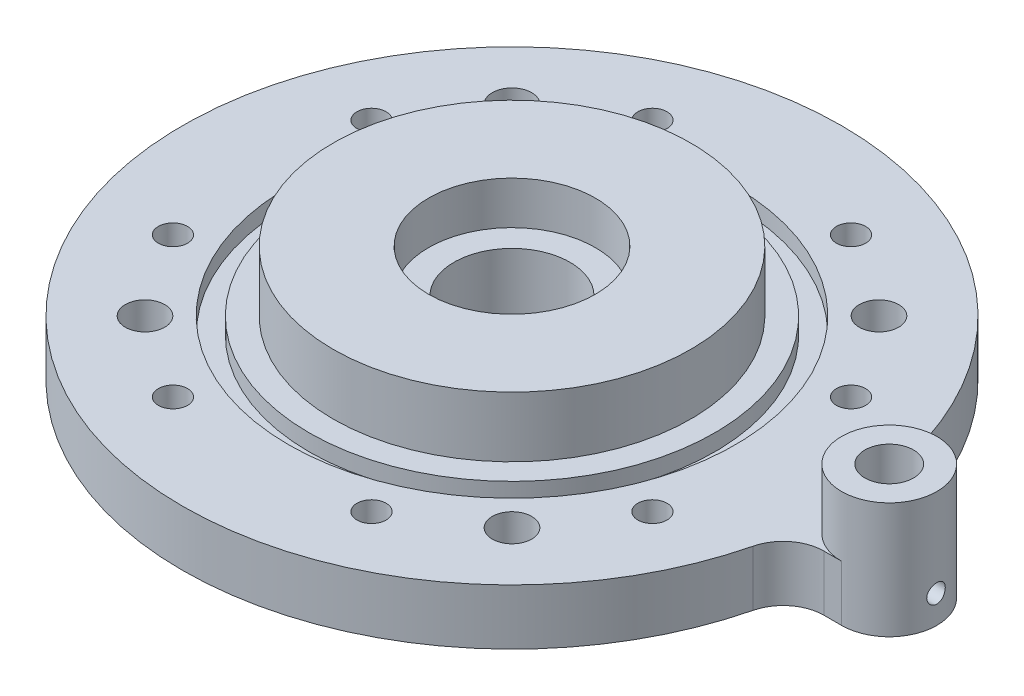
SolidWorks part; units mm, degrees
material "1060 Alloy"
ref_plane "Front" through (0, 0, 0) normal (0, 0, 1) x (1, 0, 0)
ref_plane "Top" through (0, 0, 0) normal (0, 1, 0) x (1, 0, 0)
ref_plane "Right" through (0, 0, 0) normal (1, 0, 0) x (0, 0, -1)
sketch "Sketch1" plane through (0, 0, 0) normal (0, 1, 0) x (1, 0, 0)
  line L0 (56.45, 0) -> (64.6172, 0) construction
  line L1 (61.6105, 8.1672) -> (64.6172, 8.1672)
  line L2 (61.6105, -8.1672) -> (64.6172, -8.1672)
  line L3 (56.45, 0) -> (72.7844, 0) construction
  arc A0 (54.8135, 13.4939) -> (54.8135, -13.4939) centre (0, 0) ccw
  circle A1 centre (0, 0) radius 56.45 construction
  arc A2 (64.6172, -8.1672) -> (64.6172, 8.1672) centre (64.6172, 0) ccw
  arc A3 (54.8135, 13.4939) -> (61.6105, 8.1672) centre (61.6105, 15.1672) ccw
  arc A4 (61.6105, -8.1672) -> (54.8135, -13.4939) centre (61.6105, -15.1672) ccw
  point P5 (34.5422, 0)
  point P10 (55.8561, 8.1672)
  dimension "D1" = 112.9
  dimension "D4" = 7
  dimension "D2" = 16.3344
  dimension "D3" = 16.3344
extrude "base" add sketch "Sketch1" along normal blind 9.525
sketch "Sketch2" plane through (0, 9.525, 0) normal (0, 1, 0) x (1, 0, 0)
  line L0 (64.6172, 8.1672) -> (64.6172, -8.1672) construction
  circle A0 centre (0, 0) radius 30.6267
  arc A1 (64.6172, -8.1672) -> (64.6172, 8.1672) centre (64.6172, 0) ccw construction
  circle A2 centre (64.6172, 0) radius 8.1672
  circle A3 centre (64.6172, 0) radius 4.1672
  dimension "D1" = 61.2534
  dimension "D2" = 8.3344
sketch "Sketch3" plane through (0, 0, 0) normal (0, -1, 0) x (1, 0, 0)
  line L0 (0, 0) -> (72.7844, 0) construction
  line L1 (0, 0) -> (39.9162, -39.9162) construction
  circle A0 centre (0, 0) radius 44.45 construction
  circle A1 centre (-31.4309, -31.4309) radius 3.3734
  circle A2 centre (-31.4309, 31.4309) radius 3.3734
  circle A3 centre (31.4309, 31.4309) radius 3.3734
  circle A4 centre (31.4309, -31.4309) radius 3.3734
  arc A5 (64.6172, -8.1672) -> (64.6172, 8.1672) centre (64.6172, 0) ccw construction
  arc A6 (54.8135, 13.4939) -> (54.8135, -13.4939) centre (0, 0) ccw construction
  point P14 (0, 0)
  dimension "D1" = 88.9
  dimension "D2" = 6.7469
  dimension "D4" = 45
  dimension "D3" = 4
extrude "square bolt holes" cut sketch "Sketch3" against normal through all
sketch "Sketch4" plane through (0, 9.525, 0) normal (0, 1, 0) x (1, 0, 0)
  line L0 (0, 0) -> (0, 44.45) construction
  line L1 (0, 44.45) -> (0, 0) construction
  line L2 (0, 0) -> (17.0103, 41.0664) construction
  circle A0 centre (0, 0) radius 44.45 construction
  circle A1 centre (17.0103, 41.0664) radius 2.5
  dimension "D1" = 88.9
  dimension "D3" = 5
  dimension "D2" = 22.5
extrude "housing bolts" cut sketch "Sketch4" against normal blind 44.33
pattern_circular "CirPattern1" count 8 over 360 about axis through (0, 9.525, 0) along (0, 1, 0) of "housing bolts"
extrude "impeller cavity riser" add sketch "Sketch2" along normal blind 10.3422
sketch "Sketch5" plane through (0, 19.8672, 0) normal (0, 1, 0) x (1, 0, 0)
  circle A0 centre (0, 0) radius 14.2875
  dimension "D1" = 28.575
extrude "seal bore" cut sketch "Sketch5" against normal blind 7.35
sketch "Sketch6" plane through (0, 12.5172, 0) normal (0, 1, 0) x (1, 0, 0)
  circle A0 centre (0, 0) radius 9.9375
  dimension "D1" = 19.875
extrude "bore" cut sketch "Sketch6" against normal blind 39.3
sketch "pressure tap plane alignment" plane through (0, 0, 0) normal (0, -1, 0) x (1, 0, 0)
  line L1 (0, 0) -> (56.45, 0) construction
  line L2 (56.45, 0) -> (56.45, 56.45) construction
  line L3 (56.45, 56.45) -> (0, 56.45) construction
  circle A0 centre (0, 0) radius 56.45 construction
  circle A1 centre (0, 0) radius 56.45 construction
ref_plane "pressure tap plane" through (56.45, 0, 0) normal (1, 0, 0) x (0, 0, -1)
sketch "Sketch9" plane through (56.45, 0, 0) normal (1, 0, 0) x (0, 0, -1)
  line L0 (0, 0) -> (0, 9.525) construction
  line L1 (56.45, 9.525) -> (-56.45, 9.525) construction
  circle A0 centre (0, 4.7625) radius 1.5875
  dimension "D1" = 3.175
extrude "pressure tap" cut sketch "Sketch9" against normal blind 56.45 and the other way through all
sketch "Sketch10" plane through (0, 9.525, 0) normal (0, 1, 0) x (1, 0, 0)
  circle A0 centre (64.6172, 0) radius 1.5875
  dimension "D1" = 3.175
extrude "pressure tap vertical hole" cut sketch "Sketch10" against normal blind 6.35
sketch "Sketch12" plane through (0, 9.525, 0) normal (0, 1, 0) x (1, 0, 0)
  circle A0 centre (0, 0) radius 34.7218
  circle A1 centre (0, 0) radius 38.2524
  dimension "D1" = 76.5048
  dimension "D2" = 69.4436
extrude "Cut-Extrude1" cut sketch "Sketch12" against normal blind 2.8245
equation "\"de\" = 0.426in\t\t\t'entrance eye diameter"
equation "\"d2\" = 2.097in \t\t\t'outer diameter of the impeller"
equation "\"d_exit\" = 0.18in \t\t'volute throat aka D4"
equation "\"theta\" = 25\t\t\t'angle of blades from inner to outer "
equation "\"impeller upper clearance\"= .5mm"
equation "\"impeller horizontal clearance\"= (\"d2\"*1.15 - \"d2\")/2 \t\t'clearance based on D2-D3 ratio for circular volute, ranges 1.15 to 1.2"
equation "\"impeller bottom clearance\"= .5mm"
equation "\"impeller base thickness\"= 2mm"
equation "\"impeller dowel diameter\" = 2mm"
equation "\"impeller bolt head diameter\" = \"m4 head bore diameter\""
equation "\"impeller bolt head depth\" = 4mm"
equation "\"impeller bolt stop depth\" = 3mm"
equation "\"impeller bolt bore\" = \"m4 clearance\""
equation "\"impeller shaft bore depth\" = 12mm"
equation "\"impeller shaft bore\" = 8mm"
equation "\"impeller boss depth\" = \"impeller shaft bore depth\"+\"impeller bolt stop depth\"+\"impeller bolt head depth\"-\"impeller base thickness\""
equation "\"impeller boss diameter\" = \"upper seal ID\""
equation "\"impeller dowel length\" = 2mm*2 + \"impeller shaft bore\""
equation "\"coupler motor shaft hole ID\"= 8mm"
equation "\"coupler OD\"= 17mm"
equation "\"coupler length\"= 25mm"
equation "\"motor OD\" = 64mm"
equation "\"motor shaft diameter\"= 8mm"
equation "\"motor shaft pride\"= 32mm"
equation "\"motor to bearing plate distance\" = \"motor shaft pride\" + 2mm +\"coupler length\"/2"
equation "\"square plate bolt bore\" = 8mm"
equation "\"square plate bolt head diameter\" = 13.5mm"
equation "\"square plate bolt pattern diameter\"= 3.5in"
equation "\"motor mount center bore\"= \"coupler OD\"+ 4mm"
equation "\"motor mount post radius\"= ( 3 * \"square plate bolt bore\" ) / 2"
equation "\"motor mount m4 screw hole diameter\"= 4mm"
equation "\"motor mount m4 head diameter\"= 7.25mm"
equation "\"motor mount m4 head depth\"= 4mm"
equation "\"motor mount m4 pattern diamater\" = 30mm"
equation "\"motor mount plate thickness\"= 8mm + \"motor mount m4 head depth\""
equation "\"shaft coupler section diameter\" = 8mm"
equation "\"shaft coupler section length\" = \"motor to bearing plate distance\" - \"motor shaft pride\" - 2mm"
equation "\"shaft bearing section diameter\" = \"bearing ID\""
equation "\"shaft bearing section length\" = \"bearing plate stop depth\" + \"bearing depth\""
equation "\"shaft bearing stop diameter\" = \"bearing ID\" + 4mm"
equation "\"shaft bearing stop length\" = 3mm"
equation "\"impeller cavity center height\"= \"impeller bottom clearance\" + \"impeller upper clearance\" + \"impeller center height\""
equation "\"impeller cavity diameter\"= 2 * \"impeller horizontal clearance\" + \"d2\" \t\t\t\t\t\t\t\t\t'called D3 analytically"
equation "\"impeller cavity outer height\"= \"impeller bottom clearance\" + \"impeller upper clearance\" + \"impeller base thickness\" + \"b2\" \t\t'this is height at impeller diameter d2, not at d3"
equation "\"impeller housing thickness\"= \"impeller housing exit threaded diameter\" + 2*\"impeller housing outlet grip\""
equation "\"impeller housing diameter\" = \"square plate bolt pattern diameter\" + 2*\"motor mount post radius\""
equation "\"impeller housing bolt count\" = 8"
equation "\"impeller housing bolt diameter\" = \"m6 clearance\""
equation "\"impeller housing bolt pattern diameter\" = 3.5in"
equation "\"impeller housing threaded inlet diameter\" = 0.6875in \t\t'this is the 11/16 drill size for 1/2 npt fitting"
equation "\"impeller housing threaded inlet depth\"= 15mm"
equation "\"impeller housing exit threaded diameter\"= 0.6875in \t\t'this is the 11/16 drill size for 1/2 npt fitting"
equation "\"impeller housing exit threaded depth\"= 18mm"
equation "\"impeller housing diffuser conical angle\"=10"
equation "\"impeller housing diffuser tangent angle\"=5"
equation "\"impeller housing outlet grip\" = 5mm"
equation "\"D1@Sketch1\"=\"impeller housing diameter\""
equation "\"D1@base\" = \"upper seal plate thickness\""
equation "\"D1@Sketch2\"=\"impeller cavity diameter\""
equation "\"D1@Sketch3\"=\"square plate bolt pattern diameter\""
equation "\"D2@Sketch3\"=\"m8 tap\""
equation "\"D1@square bolt holes\" = \"upper seal plate thickness\" - 2mm"
equation "\"D1@Sketch4\"=\"impeller housing bolt pattern diameter\""
equation "\"D2@Sketch4\"=360/\"impeller housing bolt count\"/2"
equation "\"D3@Sketch4\"=\"m6 tap\""
equation "\"D1@CirPattern1\"=\"impeller housing bolt count\""
equation "\"D1@impeller cavity riser\" = \"upper seal plate riser\""
equation "\"D1@Sketch5\" = \"upper seal OD\""
equation "\"D1@seal bore\" = \"upper seal bore\""
equation "\"D1@Sketch6\" = \"upper seal ID\" + 4mm"
equation "\"D1@Sketch9\" = \"upper seal plate pressure hole diameter\""
equation "\"D1@pressure tap\"=\"impeller housing diameter\"/2"
equation "\"de_length\" = 10mm\t\t'entrance eye consistent length"
equation "\"square plate bolt head depth\" = 8mm"
equation "\"shaft impeller section diameter\" = \"impeller shaft bore\""
equation "\"shaft impeller section length\" = \"upper seal plate thickness\" + \"upper seal plate riser\" + \"impeller bottom clearance\" + \"impeller base thickness\" - \"impeller bolt head depth\" - \"impeller bolt stop depth\""
equation "\"impeller housing diffuser final diameter\" = .5in"
equation "\"D2@Sketch1\" = \"upper seal plate pressure tap diameter\" + \"upper seal plate pressure tap grip\" * 2"
equation "\"D3@Sketch1\" = \"upper seal plate pressure tap diameter\" + \"upper seal plate pressure tap grip\" * 2"
equation "\"D2@pressure tap\"=\"big seal plate pressure tap diameter\"/2+\"big seal plate pressure tap grip\""
equation "\"D2@Sketch2\" = \"upper seal plate pressure tap diameter\""
equation "\"D1@Sketch10\" = \"upper seal plate pressure hole diameter\""
equation "\"D1@pressure tap vertical hole\"= \"upper seal plate thickness\" / 2 + \"upper seal plate pressure hole diameter\" / 2"
equation "\"end mill size\" = 0.375in\t'for 3/8 endmill"
equation "\"m6 clearance\" = 0.234375in\t'this is 15/64 bit = 5.95mm, could use 6mm bit, B bit for 6.04mm or 1/4 bit for 6.35mm"
equation "\"m6 tap\" = 5mm\t\t\t'5mm is appropriate, could use 13/64 or #5,6,7"
equation "\"m6 head bore diameter\" = 11mm\t\t"
equation "\"m6 head bore depth\" = 7mm\t'actual is 6mm"
equation "\"m8 clearance\" = 0.3125in\t'this is 5/16in for 7.93mm, could use 8mm, O,P, or 21/64"
equation "\"m8 tap\" = 0.265625in\t\t'this is 17/64 for 6.746875mm"
equation "\"m8 head bore diameter\" = 14mm"
equation "\"m8 head bore depth\" = 9mm\t'actual is 8mm"
equation "\"ce\" = 3.14*\"de\"\t\t'entrance eye circumference"
equation "\"s_open\" = \"av\"/\"b1\"\t\t'width of open area"
equation "\"impeller center height\" = \"impeller base thickness\" + \"b1\"\t'impeller height at de"
equation "\"impeller outer height\" = \"impeller base thickness\" + \"b2\"\t'impeller height at de"
equation "\"lower seal OD\" = .917in\t\t'this is https://www.mcmaster.com/#9281k121/=174001b"
equation "\"lower seal ID\"= .375in"
equation "\"lower seal depth\" = .625in + .218in"
equation "\"lower seal bore\" = \"lower seal depth\" + 1mm"
equation "\"upper seal OD\" = 1.125in\t'this is https://www.mcmaster.com/#5154t33/=173zuau, needs to be visually inspected before machining!"
equation "\"upper seal ID\"= 0.625in"
equation "\"upper seal depth\"= .25in\t'aka height; these values need to be confirmed by inspection!! We may want to compress the height."
equation "\"upper seal bore\" = \"upper seal depth\" + 1mm"
equation "\"lower seal plate lip depth\" = 2mm"
equation "\"lower seal plate lip ID\" = \"lower seal OD\" - 3mm"
equation "\"lower seal plate thickness\" = \"lower seal plate lip depth\" + \"lower seal bore\""
equation "\"shaft lower seal section diameter\" = \"lower seal ID\""
equation "\"shaft lower seal section length\" = \"lower seal plate thickness\" + 1mm"
equation "\"upper seal plate thickness\" = \"upper seal plate pressure hole diameter\"*3"
equation "\"upper seal plate lip ID\" = \"upper seal OD\" - 3mm"
equation "\"upper seal plate riser\" = \"impeller housing thickness\"/2 - \"b2\"/2 - \"impeller base thickness\" - \t\"impeller bottom clearance\"\t\t\t'this offsets the gap under the housing"
equation "\"upper seal plate pressure hole diameter\" = .125in\t'this is 1/8 drill "
equation "\"upper seal plate pressure tap diameter\" = .328125in \t'this is 21/64 drill for a 1/8 ANPT tap"
equation "\"upper seal plate pressure tap grip\" = 4mm\t\t'this is the area around the tap so it doesn't crack"
equation "\"upper seal plate pressure tap depth\" = 12"
equation "\"bearing OD\" = 30mm"
equation "\"bearing ID\"= 10mm"
equation "\"bearing depth\"= 9mm"
equation "\"bearing outer race thickness\"= 1mm"
equation "\"bearing inner race thickness\"= 1mm"
equation "\"bearing bore\" = \"bearing depth\" + 1mm"
equation "\"z\" = 8 \t\t\t'number of blades"
equation "\"b2\" = .07in\t\t\t\t\t\t\t'tip height from disc surface at d2"
equation "\"b1\" = \"b2\" + (\"d2\"/2 - \"de\"/2)*tan(\"theta\") \t\t\t'tip height from disc surface at inlet eye"
equation "\"ae\" = 3.14*(\"de\"^2)/4\t\t'entrance eye area'"
equation "\"av_ratio\" = .325\t\t'ratio of av/ae at N_s of 470, range is .275 to .375, .325 ideal. High ratio means bigger area means smaller blades"
equation "\"av\" = \"ae\"*\"av_ratio\"\t\t'area between just two blades"
equation "\"s\"=\"ce\" - \"z\"*\"s_open\""
equation "\"bearing plate stop ID\" = \"bearing OD\" - 4mm"
equation "\"bearing plate stop depth\" = 3mm"
equation "\"bearing plate thickness\" = \"bearing bore\" + \"bearing plate stop depth\" + \"shaft bearing stop length\""
equation "\"m4 clearance\" = 0.171875in \t'this is 11/64 bit for 4.36mm"
equation "\"m4 tap\" = 0.125in\t\t'this is 1/8 bit for 3.17mm"
equation "\"m4 head bore diameter\" = 7.5mm"
equation "\"m4 head bore depth\" = 5mm\t'actual is ~4mm"
equation "\"big o-ring thickness\" = .139in"
equation "\"big o-ring OD\" = 2.734in"
equation "\"big o-ring ID\" = 3.012in"
equation "\"big o-ring groove depth\" = \"big o-ring thickness\"*4/5"
equation "\"D1@Sketch12\"=\"big o-ring ID\""
equation "\"D2@Sketch12\"=\"big o-ring OD\""
equation "\"D1@Cut-Extrude1\"=\"big o-ring groove depth\""
